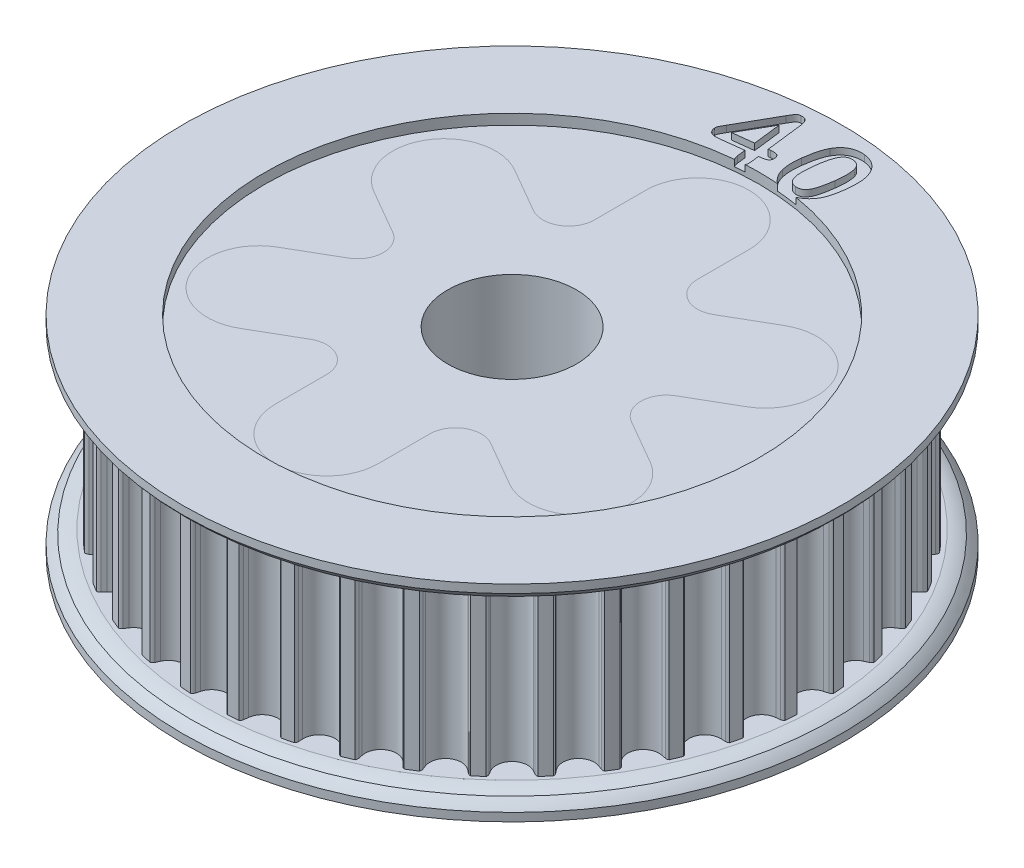
SolidWorks part; units mm, degrees
other "DetailItem2"
material "Markforged"
ref_plane "Front Plane" through (0, 0, 0) normal (0, 0, 1) x (1, 0, 0)
ref_plane "Top Plane" through (0, 0, 0) normal (0, 1, 0) x (1, 0, 0)
ref_plane "Right Plane" through (0, 0, 0) normal (1, 0, 0) x (0, 0, -1)
ref_axis "Centerline" through (0, 8.7312, 0) along (0, -1, 0)
sketch "Sketch1" plane through (0, 0, 0) normal (0, 1, 0) x (1, 0, 0)
  circle A0 centre (0, 0) radius 18.7176
  dimension "OuterDiameter" = 37.4352
extrude "ToothOD" add sketch "Sketch1" along normal mid plane 10.16
sketch "Sketch2" plane through (0, 0, 0) normal (0, 1, 0) x (1, 0, 0)
  line L0 (0, 17.5492) -> (50000, 17.5492) construction
  line L1 (0, 18.7176) -> (50000, 18.7176) construction
  line L2 (0, 0) -> (0, 50000) construction
  arc A0 (-0.937, 18.2677) -> (0, 17.5492) centre (0, 18.5195) ccw
  arc A1 (-1.1278, 18.6836) -> (1.1278, 18.6836) centre (0, 0) cw
  circle A2 centre (0, 0) radius 18.7176 construction
  arc A3 (-0.937, 18.2677) -> (-1.0078, 18.5195) centre (-11.9754, 15.3012) ccw
  arc A4 (-1.0078, 18.5195) -> (-1.1278, 18.6836) centre (-1.2954, 18.4351) ccw
  circle A5 centre (0, 0) radius 18.7176 construction
  arc A6 (0.937, 18.2677) -> (1.0078, 18.5195) centre (11.9754, 15.3012) cw
  arc A7 (1.0078, 18.5195) -> (1.1278, 18.6836) centre (1.2954, 18.4351) cw
  arc A8 (0, 17.5492) -> (0.937, 18.2677) centre (0, 18.5195) ccw
  dimension "D1" = 1.9406
  dimension "D3" = 22.86
  dimension "D4" = 0.5994
  dimension "D2" = 1.1684
  dimension "D5" = 1.2954
extrude "ToothProfile" cut sketch "Sketch2" against normal through all both and the other way through all
pattern_circular "ToothPattern" count 40 over 360 about axis through (0, 5.08, 0) along (0, -1, 0) of "ToothProfile"
sketch "Sketch4" plane through (0, 0, 0) normal (0, 0, 1) x (1, 0, 0)
  line L0 (0, -5.08) -> (18.9716, -5.08)
  line L1 (0, -6.35) -> (20.32, -6.35)
  line L2 (0, -6.35) -> (0, -5.08)
  line L3 (20.32, -6.35) -> (20.32, -5.842)
  line L4 (0, 0) -> (50000, 0) construction
  line L5 (20.32, 6.35) -> (20.32, 5.842)
  line L6 (0, 6.35) -> (0, 5.08)
  line L7 (0, 6.35) -> (20.32, 6.35)
  line L8 (0, 5.08) -> (18.9716, 5.08)
  arc A0 (18.9716, -5.08) -> (19.812, -5.334) centre (18.6641, -7.6148) cw
  arc A2 (19.812, -5.334) -> (20.32, -5.842) centre (17.815, -7.839) cw
  arc A3 (19.812, 5.334) -> (20.32, 5.842) centre (17.815, 7.839) ccw
  arc A4 (18.9716, 5.08) -> (19.812, 5.334) centre (18.6641, 7.6148) ccw
  dimension "D5" = 2.5534
  dimension "D6" = 3.2036
  dimension "FlangeID" = 18.9716
  dimension "D2" = 0.508
  dimension "D3" = 5.08
  dimension "D4" = 12.7
  dimension "D7" = 0.762
  dimension "D8" = 0.508
  dimension "D10" = 0.508
  dimension "D9" = 20.32
revolve "Flange" add sketch "Sketch4" angle 360 about axis through (0, 8.7312, 0) along (0, -1, 0)
sketch "Sketch6" plane through (0, 0, 0) normal (0, 0, 1) x (1, 0, 0)
  line L0 (0, -6.35) -> (0, -7.9375) construction
  line L1 (-20.32, -6.35) -> (20.32, -6.35) construction
  line L2 (0, -7.9375) -> (6.7056, -7.9375) construction
  line L3 (6.7056, -7.9375) -> (6.7056, -6.35) construction
  line L4 (6.7056, -6.35) -> (0, -6.35) construction
  line L5 (0, 0) -> (50000, 0) construction
  line L6 (6.7056, 6.35) -> (0, 6.35)
  line L7 (6.7056, 7.9375) -> (6.7056, 6.35)
  line L8 (0, 7.9375) -> (6.7056, 7.9375)
  line L9 (0, 6.35) -> (0, 7.9375)
  line L11 (34.4843, 11.0952) -> (29.5547, 13.6304) construction
  line L12 (29.5547, 13.6304) -> (24.8944, 10.6289) construction
  line L13 (24.8944, 10.6289) -> (25.1637, 5.0922) construction
  line L14 (25.1637, 5.0922) -> (30.0933, 2.557) construction
  line L15 (30.0933, 2.557) -> (34.7536, 5.5585) construction
  line L16 (34.7536, 5.5585) -> (34.4843, 11.0952) construction
  circle A0 centre (29.824, 8.0937) radius 4.8006 construction
  circle A1 centre (29.824, 8.0937) radius 6.7056 construction
  dimension "D2" = 9.6012
  dimension "D1" = 15.875
  dimension "D4" = 6.7056
  dimension "D3" = 1.905
  dimension "D5" = 1.5875
revolve "TopBearingBoss" [suppressed] add sketch "Sketch6" angle 360 about axis through (0, 8.7312, 0) along (0, -1, 0)
mirror "BottomBearingBoss" [suppressed] about plane through (0, 0, 0) normal (0, 1, 0)
sketch "Sketch7" plane through (0, 0, 0) normal (0, -1, 0) x (1, 0, 0)
  circle A0 centre (0, 0) radius 3.9688
  dimension "D1" = 7.9375
extrude "Bore" cut sketch "Sketch7" against normal through all both and the other way through all
sketch "Sketch9" plane through (0, 6.35, 0) normal (0, 1, 0) x (1, 0, 0)
  arc A0 (-10.7763, -10.7763) -> (10.7763, -10.7763) centre (0, 0) cw construction
  text T0 "40" font "Arial Rounded MT Bold" height 4.572
  point P3 (0, 15.24)
  dimension "D1" = 15.24
  dimension "D2" = 270
extrude "Large Tooth Count" cut sketch "Sketch9" against normal blind 0.4 and the other way through all
sketch "Sketch11" plane through (0, 6.35, 0) normal (0, 1, 0) x (1, 0, 0)
  arc A0 (-4.8314, -4.8314) -> (4.8314, -4.8314) centre (0, 0) cw construction
  text T0 "<b>40</b>" font "Arial Rounded MT Bold" height 2.286
  point P6 (0, 6.8326)
  dimension "D4" = 6.8326
  dimension "D3" = 270
extrude "Small Tooth Count" [suppressed] cut sketch "Sketch11" against normal blind 0.4 and the other way through all
sketch "Sketch14" plane through (0, 0, 0) normal (0, 0, 1) x (1, 0, 0)
  line L0 (20.32, 6.35) -> (-20.32, 6.35) construction
  line L1 (0, 6.35) -> (15.24, 6.35)
  line L2 (0, 6.35) -> (0, 5.715)
  line L3 (0, 5.715) -> (15.24, 5.715)
  line L4 (15.24, 6.35) -> (15.24, 5.715)
  line L5 (0, 6.35) -> (15.24, 5.715) construction
  line L6 (0, 5.715) -> (15.24, 6.35) construction
  line L7 (-20.32, -6.35) -> (20.32, -6.35) construction
  line L8 (0, -6.35) -> (15.24, -6.35)
  line L9 (0, -6.35) -> (0, -3.81)
  line L10 (0, -3.81) -> (15.24, -3.81)
  line L11 (15.24, -6.35) -> (15.24, -3.81)
  line L12 (0, -6.35) -> (15.24, -3.81) construction
  line L13 (0, -3.81) -> (15.24, -6.35) construction
  line L14 (0, 0) -> (0, 50000) construction
  point P4 (7.62, 6.0325)
  point P11 (7.62, -5.08)
  dimension "D1" = 9.525
  dimension "D2" = 15.24
  dimension "D3" = 2.54
revolve "Cut-Revolve1" cut sketch "Sketch14" angle 360 about L14
sketch "Sketch15" plane through (0, -6.35, 0) normal (0, -1, 0) x (1, 0, 0)
  line L0 (0, 0) -> (0, 11.43) construction
  line L1 (-3.175, 0) -> (-3.175, 11.43)
  line L2 (3.175, 0) -> (3.175, 11.43)
  arc A0 (-3.175, 0) -> (3.175, 0) centre (0, 0) ccw
  arc A1 (3.175, 11.43) -> (-3.175, 11.43) centre (0, 11.43) ccw
  point P3 (0, 5.715)
  dimension "D1" = 3.175
  dimension "D2" = 11.43
extrude "Cut-Extrude1" cut sketch "Sketch15" against normal through all
pattern_circular "CirPattern1" count 6 over 360 about axis through (0, 6.35, 0) along (0, -1, 0) of "Cut-Extrude1"
fillet "Fillet1" radius 1.5875 6 edges at (-6.35, 0.9525, 0) (-3.175, 0.9525, -5.4993) (3.175, 0.9525, -5.4993) (6.35, 0.9525, 0) (-3.175, 0.9525, 5.4993) (3.175, 0.9525, 5.4993)
sketch "Sketch17" plane through (0, -3.81, 0) normal (0, -1, 0) x (1, 0, 0)
  line L14 (3.175, 8.2489) -> (3.175, 11.43)
  line L16 (8.3112, 8.4646) -> (5.5563, 6.8741)
  line L18 (8.7312, 1.3748) -> (11.4862, 2.9654)
  line L20 (11.4862, -2.9654) -> (8.7312, -1.3748)
  line L22 (5.5562, -6.8741) -> (8.3112, -8.4646)
  line L24 (3.175, -11.43) -> (3.175, -8.2489)
  line L26 (-3.175, -8.2489) -> (-3.175, -11.43)
  line L28 (-8.3112, -8.4646) -> (-5.5563, -6.8741)
  line L30 (-8.7312, -1.3748) -> (-11.4862, -2.9654)
  line L32 (-11.4862, 2.9654) -> (-8.7312, 1.3748)
  line L34 (-5.5562, 6.8741) -> (-8.3112, 8.4646)
  line L37 (-3.175, 11.43) -> (-3.175, 8.2489)
  line L50 (3.175, 8.2489) -> (3.175, 11.43)
  line L51 (8.3112, 8.4646) -> (5.5563, 6.8741)
  line L52 (8.7312, 1.3748) -> (11.4862, 2.9654)
  line L53 (11.4862, -2.9654) -> (8.7312, -1.3748)
  line L54 (5.5562, -6.8741) -> (8.3112, -8.4646)
  line L55 (3.175, -11.43) -> (3.175, -8.2489)
  line L56 (-3.175, -8.2489) -> (-3.175, -11.43)
  line L57 (-8.3112, -8.4646) -> (-5.5563, -6.8741)
  line L58 (-8.7312, -1.3748) -> (-11.4862, -2.9654)
  line L59 (-11.4862, 2.9654) -> (-8.7312, 1.3748)
  line L60 (-5.5562, 6.8741) -> (-8.3112, 8.4646)
  line L61 (-3.175, 11.43) -> (-3.175, 8.2489)
  circle A1 centre (0, 0) radius 3.9688 construction
  circle A8 centre (0, 0) radius 3.9688
  arc A47 (3.175, 8.2489) -> (5.5563, 6.8741) centre (4.7625, 8.2489) ccw
  arc A48 (11.4862, 2.9654) -> (8.3112, 8.4646) centre (9.8987, 5.715) ccw
  arc A49 (8.7312, 1.3748) -> (8.7312, -1.3748) centre (9.525, 0) ccw
  arc A50 (8.3112, -8.4646) -> (11.4862, -2.9654) centre (9.8987, -5.715) ccw
  arc A51 (5.5562, -6.8741) -> (3.175, -8.2489) centre (4.7625, -8.2489) ccw
  arc A52 (-3.175, -11.43) -> (3.175, -11.43) centre (0, -11.43) ccw
  arc A53 (-3.175, -8.2489) -> (-5.5563, -6.8741) centre (-4.7625, -8.2489) ccw
  arc A54 (-11.4862, -2.9654) -> (-8.3112, -8.4646) centre (-9.8987, -5.715) ccw
  arc A55 (-8.7312, -1.3748) -> (-8.7312, 1.3748) centre (-9.525, 0) ccw
  arc A56 (-8.3112, 8.4646) -> (-11.4862, 2.9654) centre (-9.8987, 5.715) ccw
  arc A57 (-5.5562, 6.8741) -> (-3.175, 8.2489) centre (-4.7625, 8.2489) ccw
  arc A70 (3.175, 11.43) -> (-3.175, 11.43) centre (0, 11.43) ccw
  arc A71 (3.175, 8.2489) -> (5.5563, 6.8741) centre (4.7625, 8.2489) ccw
  arc A72 (11.4862, 2.9654) -> (8.3112, 8.4646) centre (9.8987, 5.715) ccw
  arc A73 (8.7312, 1.3748) -> (8.7312, -1.3748) centre (9.525, 0) ccw
  arc A74 (8.3112, -8.4646) -> (11.4862, -2.9654) centre (9.8987, -5.715) ccw
  arc A75 (5.5562, -6.8741) -> (3.175, -8.2489) centre (4.7625, -8.2489) ccw
  arc A76 (-3.175, -11.43) -> (3.175, -11.43) centre (0, -11.43) ccw
  arc A77 (-3.175, -8.2489) -> (-5.5563, -6.8741) centre (-4.7625, -8.2489) ccw
  arc A78 (-11.4862, -2.9654) -> (-8.3112, -8.4646) centre (-9.8987, -5.715) ccw
  arc A79 (-8.7312, -1.3748) -> (-8.7312, 1.3748) centre (-9.525, 0) ccw
  arc A80 (-8.3112, 8.4646) -> (-11.4862, 2.9654) centre (-9.8987, 5.715) ccw
  arc A81 (-5.5562, 6.8741) -> (-3.175, 8.2489) centre (-4.7625, 8.2489) ccw
  arc A82 (3.175, 11.43) -> (-3.175, 11.43) centre (0, 11.43) ccw
  dimension "D1" = 0
extrude "Boss-Extrude1" add sketch "Sketch17" against normal up to surface (9.525 mm away) separate body up to face at (0, 5.715, 0)
sketch "Sketch21" plane through (0, -3.81, 0) normal (0, -1, 0) x (1, 0, 0)
  circle A0 centre (0, 0) radius 6.35
  dimension "D1" = 12.7
extrude "Cut-Extrude4" cut sketch "Sketch21" against normal blind 2.286
equation "\"OuterDiameter@Sketch1\"= \"OD\""
equation "\"Teeth\"= \"No_Teeth\""
equation "\"PD\"= \"No_Teeth\" * 3mm / pi"
equation "\"OD\"= \"PD\" - .030"
equation "\"ToothCount@ToothPattern\" = \"Teeth\""
equation "\"Angle\"= 360 / \"Teeth\""
equation "\"AngleSpacing@ToothPattern\" = \"Angle\""
equation "\"FlangeID@Sketch4\"=\"OD\"/2+.01"
equation "\"D3@Sketch4\"=\"Tooth_Face_Length\"/2"
equation "\"Bearing_Feature\"= \"Bearing_Boss\""
equation "\"TopBearingBoss\" = IIF ( \"Bearing_Feature\" > 0 , \"unsuppressed\" , \"suppressed\" )"
equation "\"HexBore\"= \"Hex_Bore\" + \"Print_Tolerance\""
equation "\"D2@Sketch6\"=\"HexBore\""
equation "\"D4@Sketch6\"=\"HexBore\"/2+.075"
equation "\"Large Tooth Count\" = iif ( \"No_Teeth\" < \"TextTooth\" , \"suppressed\" , \"unsuppressed\" )"
equation "\"Small Tooth Count\"= iif ( \"No_Teeth\" < \"TextTooth\" , \"unsuppressed\" , \"suppressed\" )"
equation "\"BottomBearingBoss\" = iif ( \"Bearing_Feature\" > 1 , \"unsuppressed\" , \"suppressed\" )"
equation "\"ToothFaceLength@ToothOD\" = \"Tooth_Face_Length\""
equation "\"D4@Sketch4\" = \"Width_No_BearingBoss\""
equation "\"TextTooth\"= iif ( \"Hex_Bore\" <= .380 , 23 , iif ( \"Hex_Bore\" <= .505 , 25 , 16 ) )"
equation "\"D4@Sketch11\"=\"HexBore\"/2+.08"
equation "\"D1@Sketch6\"=\"Overall_Width\""
